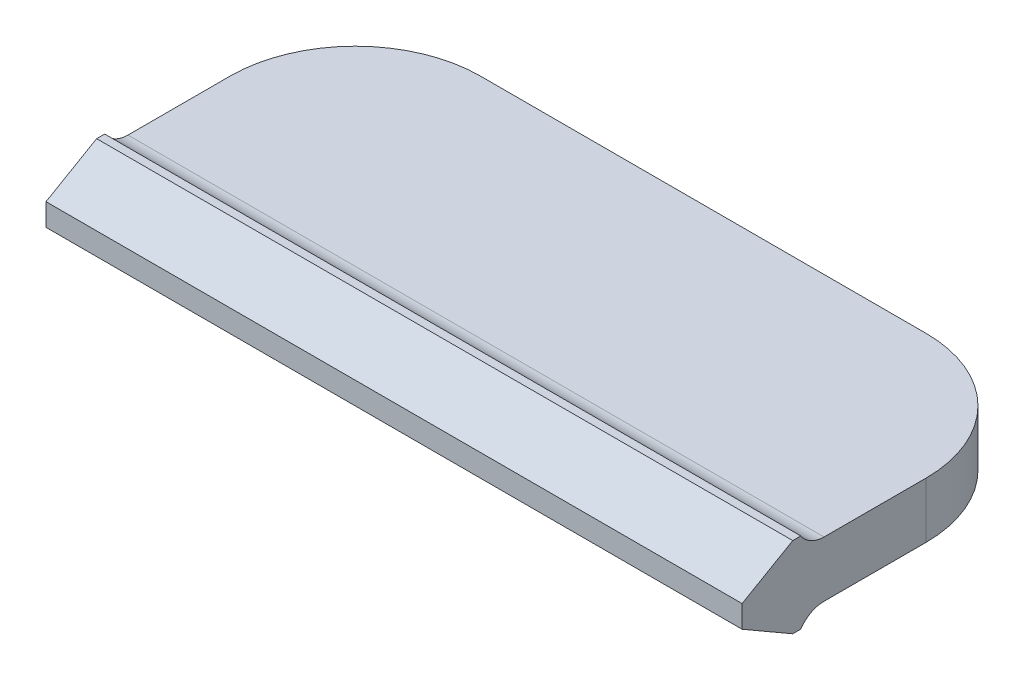
SolidWorks part; units mm, degrees
ref_plane "Top" through (0, 0, 0) normal (0, 0, 1) x (1, 0, 0)
ref_plane "Front" through (0, 0, 0) normal (0, 1, 0) x (1, 0, 0)
ref_plane "Right" through (0, 0, 0) normal (1, 0, 0) x (0, 0, -1)
sketch "Connection Sketch" plane through (0, 0, 0) normal (1, 0, 0) x (0, 0, -1)
  line L0 (0, 1.45) -> (0, 1)
  line L1 (0, -1.6) -> (-0.3287, -1.6) construction
  line L2 (-0.3287, -1.6) -> (-3.1, 0) construction
  line L5 (-3.1, 0) -> (-0.3287, 1.6) construction
  line L6 (-0.3287, 1.6) -> (0, 1.6) construction
  line L7 (-3.1, 0) -> (0, 0) construction
  line L8 (-3.1, 0) -> (-3.1, 1.6) construction
  line L11 (0, 1.45) -> (-0.2885, 1.45)
  line L12 (-0.2885, 1.45) -> (-2.1072, 0.4)
  line L13 (-2.1072, 0.4) -> (-2.1072, -0.4)
  line L14 (-2.1072, -0.4) -> (-0.2885, -1.45)
  line L15 (-0.2885, -1.45) -> (0, -1.45)
  line L16 (0, 1.6) -> (0, 1.45) construction
  line L17 (0, -1.45) -> (0, -1.6) construction
  line L18 (0, -1) -> (9, -1)
  line L19 (9, -1) -> (9, 1)
  line L20 (9, 1) -> (0, 1)
  line L21 (0, -1) -> (0, -1.45)
  line L22 (0, -1) -> (0, 1) construction
  dimension "D1" = 60
  dimension "D2" = 3.2
  dimension "D7" = 0.8
  dimension "D8" = 3.1
  dimension "D4" = 0.15
  dimension "D3" = 0.15
  dimension "D6" = 0.15
  dimension "D5" = 0.15
  dimension "D9" = 0.3287
  dimension "D10" = 2
  dimension "D11" = 9
extrude "Connection Extrude" add sketch "Connection Sketch" along normal blind 25 separate body
fillet "Top Fillets" radius 4.5 2 edges at (25, 0, -9) (0, 0, -9)
fillet "Connection Fillets" radius 1 2 edges at (12.5, 1, 0) (12.5, -1, 0)
equation "\"Handle Thickness\"= 2"
equation "\"Connection Chamfer Angle\"= 60deg"
equation "\"Connecion Clearance\"= 0.15mm"
equation "\"D1@Connection Sketch\"=\"Connection Chamfer Angle\""
equation "\"D4@Connection Sketch\"=\"Connecion Clearance\""
equation "\"D3@Connection Sketch\"=\"Connecion Clearance\""
equation "\"D6@Connection Sketch\"=\"Connecion Clearance\""
equation "\"D5@Connection Sketch\"=\"Connecion Clearance\""
equation "\"D10@Connection Sketch\"=\"Handle Thickness\""
